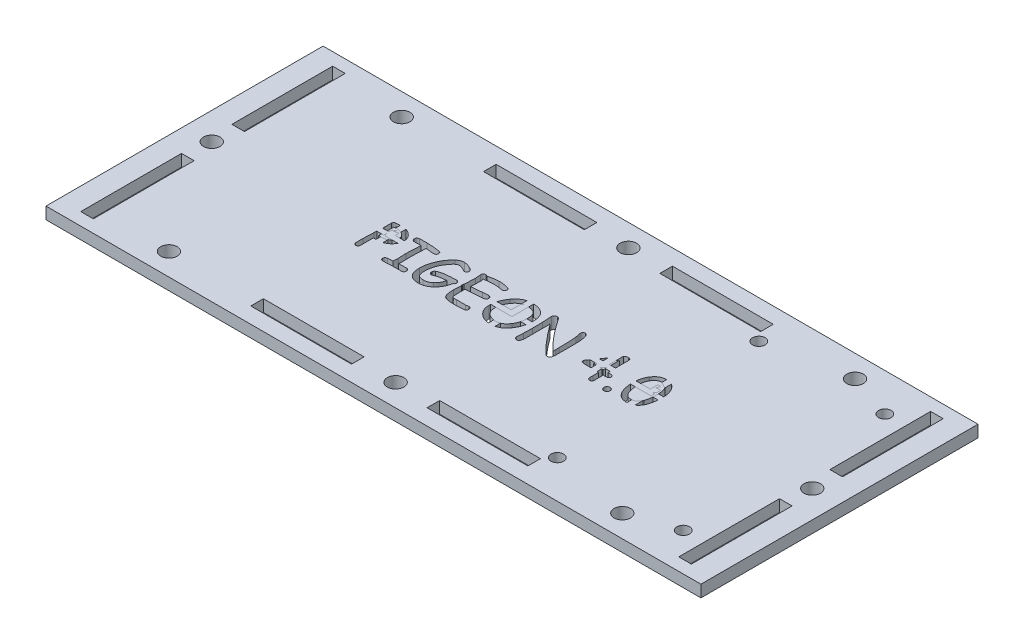
SolidWorks part; units mm, degrees
material "Thornel VCB-20 Carbon Cloth"
ref_plane "Front Plane" through (0, 0, 0) normal (0, 0, 1) x (1, 0, 0)
ref_plane "Top Plane" through (0, 0, 0) normal (0, 1, 0) x (1, 0, 0)
ref_plane "Right Plane" through (0, 0, 0) normal (1, 0, 0) x (0, 0, -1)
sketch "Sketch1" plane through (0, 0, 0) normal (0, 1, 0) x (1, 0, 0)
  line L1 (-82.55, -34.925) -> (82.55, -34.925)
  line L2 (-82.55, -34.925) -> (-82.55, 34.925)
  line L3 (-82.55, 34.925) -> (82.55, 34.925)
  line L4 (82.55, -34.925) -> (82.55, 34.925)
  dimension "D1" = 69.85
  dimension "D2" = 165.1
  dimension "D3" = 34.925
  dimension "D4" = 82.55
extrude "Boss-Extrude1" add sketch "Sketch1" along normal blind 3
sketch "Sketch2" plane through (0, 3, 0) normal (0, 1, 0) x (1, 0, 0)
  line L0 (-82.55, 34.925) -> (-82.55, -34.925) construction
  line L1 (82.55, -34.925) -> (82.55, 34.925) construction
  line L2 (82.55, 34.925) -> (-82.55, 34.925) construction
  line L3 (-82.55, -34.925) -> (82.55, -34.925) construction
  circle A0 centre (-77.47, 29.845) radius 1.5
  circle A1 centre (-77.47, -29.845) radius 1.5
  circle A2 centre (77.47, 29.845) radius 1.5
  circle A3 centre (77.47, -29.845) radius 1.5
  dimension "D1" = 3
  dimension "D2" = 3
  dimension "D3" = 3
  dimension "D4" = 3
  dimension "D5" = 5.08
  dimension "D6" = 5.08
  dimension "D7" = 5.08
  dimension "D8" = 5.08
  dimension "D9" = 5.08
  dimension "D10" = 5.08
  dimension "D11" = 5.08
  dimension "D12" = 5.08
sketch "Sketch3" plane through (0, 3, 0) normal (0, 1, 0) x (1, 0, 0)
  line L0 (-82.55, 34.925) -> (-82.55, -34.925) construction
  line L1 (82.55, -34.925) -> (82.55, 34.925) construction
  line L2 (-82.55, -34.925) -> (82.55, -34.925) construction
  line L3 (82.55, 34.925) -> (-82.55, 34.925) construction
  circle A0 centre (-75.692, 0) radius 2.0828
  circle A1 centre (75.692, 0) radius 2.0828
  circle A2 centre (0, -29.337) radius 2.0828
  circle A3 centre (0, 29.337) radius 2.0828
  circle A4 centre (57.15, 29.337) radius 2.0828
  circle A5 centre (57.15, -29.337) radius 2.0828
  circle A6 centre (-57.15, -29.337) radius 2.0828
  circle A7 centre (-57.15, 29.337) radius 2.0828
  dimension "D1" = 6.858
  dimension "D2" = 6.858
  dimension "D3" = 5.588
  dimension "D4" = 5.588
  dimension "D5" = 2
  dimension "D6" = 2
extrude "Cut-Extrude2" cut sketch "Sketch3" against normal blind 5.08
sketch "Sketch4" plane through (0, 3, 0) normal (0, 1, 0) x (1, 0, 0)
  line L0 (-82.55, 34.925) -> (-82.55, -34.925) construction
  line L1 (-44.31, -29) -> (-67.31, -29) construction
  line L2 (-44.31, -29) -> (-44.31, 29) construction
  line L3 (-44.31, 29) -> (-67.31, 29) construction
  line L4 (-67.31, -29) -> (-67.31, 29) construction
  line L5 (-44.31, -29) -> (-67.31, 29) construction
  line L6 (-44.31, 29) -> (-67.31, -29) construction
  circle A0 centre (-67.31, 29) radius 1.625
  circle A1 centre (-44.31, 29) radius 1.625
  circle A2 centre (-44.31, -29) radius 1.625
  circle A3 centre (-67.31, -29) radius 1.625
  point P0 (-55.81, 0)
  dimension "D3" = 3.25
  dimension "D1" = 58
  dimension "D2" = 23
  dimension "D4" = 15.24
sketch "Sketch5" plane through (0, 3, 0) normal (0, 1, 0) x (1, 0, 0)
  line L0 (82.55, 34.925) -> (-82.55, 34.925) construction
  line L1 (68.58, -25.4) -> (36.83, -25.4) construction
  line L2 (68.58, -25.4) -> (68.58, 25.4) construction
  line L3 (68.58, 25.4) -> (36.83, 25.4) construction
  line L4 (36.83, -25.4) -> (36.83, 25.4) construction
  line L5 (68.58, -25.4) -> (36.83, 25.4) construction
  line L6 (68.58, 25.4) -> (36.83, -25.4) construction
  line L7 (-82.55, -34.925) -> (82.55, -34.925) construction
  line L8 (82.55, -34.925) -> (82.55, 34.925) construction
  circle A0 centre (68.58, -25.4) radius 1.5875
  circle A2 centre (68.58, 25.4) radius 1.5875
  circle A3 centre (36.83, 25.4) radius 1.5875
  circle A4 centre (36.83, -25.4) radius 1.5875
  point P0 (52.705, 0)
  dimension "D1" = 9.525
  dimension "D3" = 3.175
  dimension "D2" = 9.525
  dimension "D4" = 31.75
  dimension "D5" = 13.97
extrude "Cut-Extrude4" cut sketch "Sketch5" against normal blind 7.874
sketch "Sketch6" plane through (0, 3, 0) normal (0, 1, 0) x (1, 0, 0)
  line L0 (82.55, 34.925) -> (-82.55, 34.925) construction
  line L1 (-34.925, 27.7495) -> (-9.525, 27.7495)
  line L2 (-34.925, 27.7495) -> (-34.925, 30.9245)
  line L3 (-34.925, 30.9245) -> (-9.525, 30.9245)
  line L4 (-9.525, 27.7495) -> (-9.525, 30.9245)
  line L5 (-34.925, 27.7495) -> (-9.525, 30.9245) construction
  line L6 (-34.925, 30.9245) -> (-9.525, 27.7495) construction
  line L7 (34.925, 30.9245) -> (34.925, 27.7495)
  line L8 (34.925, 30.9245) -> (9.525, 30.9245)
  line L9 (9.525, 30.9245) -> (9.525, 27.7495)
  line L10 (34.925, 27.7495) -> (9.525, 27.7495)
  line L11 (-34.925, -30.9245) -> (-34.925, -27.7495)
  line L12 (-34.925, -27.7495) -> (-9.525, -27.7495)
  line L13 (-9.525, -30.9245) -> (-9.525, -27.7495)
  line L14 (-34.925, -30.9245) -> (-9.525, -30.9245)
  line L15 (34.925, -27.7495) -> (34.925, -30.9245)
  line L16 (34.925, -27.7495) -> (9.525, -27.7495)
  line L17 (9.525, -27.7495) -> (9.525, -30.9245)
  line L18 (34.925, -30.9245) -> (9.525, -30.9245)
  line L19 (-82.55, 34.925) -> (-82.55, -34.925) construction
  line L20 (-76.962, 31.75) -> (-73.787, 31.75)
  line L21 (-76.962, 31.75) -> (-76.962, 6.35)
  line L22 (-76.962, 6.35) -> (-73.787, 6.35)
  line L23 (-73.787, 31.75) -> (-73.787, 6.35)
  line L24 (-76.962, 31.75) -> (-73.787, 6.35) construction
  line L25 (-76.962, 6.35) -> (-73.787, 31.75) construction
  line L26 (-76.962, -6.35) -> (-76.962, -31.75)
  line L27 (-76.962, -6.35) -> (-73.787, -6.35)
  line L28 (-73.787, -6.35) -> (-73.787, -31.75)
  line L29 (-76.962, -31.75) -> (-73.787, -31.75)
  line L30 (-82.55, -34.925) -> (82.55, -34.925) construction
  line L31 (76.962, -31.75) -> (76.962, -6.35)
  line L32 (76.962, -31.75) -> (73.787, -31.75)
  line L33 (73.787, -31.75) -> (73.787, -6.35)
  line L34 (76.962, -6.35) -> (73.787, -6.35)
  line L35 (76.962, 6.35) -> (76.962, 31.75)
  line L36 (76.962, 31.75) -> (73.787, 31.75)
  line L37 (73.787, 6.35) -> (73.787, 31.75)
  line L38 (76.962, 6.35) -> (73.787, 6.35)
  circle A0 centre (0, 29.337) radius 2.0828 construction
  point P0 (-22.225, 29.337)
  point P9 (-75.3745, 19.05)
  point P16 (0, 29.337)
  point P25 (0, 0)
  point P41 (0, 0)
  point P48 (0, 0)
  dimension "D1" = 5.588
  dimension "D2" = 3.175
  dimension "D3" = 25.4
  dimension "D4" = 22.225
  dimension "D7" = 5.588
  dimension "D8" = 3.175
  dimension "D9" = 25.4
  dimension "D10" = 3.175
  dimension "D12" = 3.175
  dimension "D11" = 2
  dimension "D5" = 2
  dimension "D6" = 2
  dimension "D13" = 2
extrude "Cut-Extrude5" cut sketch "Sketch6" against normal blind 10.922
sketch "Sketch7" plane through (0, 3, 0) normal (0, 1, 0) x (1, 0, 0)
  text T0 "PIGEON 4.0" font "Comic Sans MS" height 9.525
  point P1 (-47.03, 0)
  point P6 (-47.03, 0)
extrude "Cut-Extrude6" cut sketch "Sketch7" against normal blind 10.922
sketch "Sketch8" plane through (0, 3, 0) normal (0, 1, 0) x (1, 0, 0)
  line L0 (-37.8032, 1.2942) -> (-33.6782, 1.2942)
  line L1 (-37.8032, 1.2942) -> (-37.8032, 2.6847)
  line L2 (-37.8032, 2.6847) -> (-33.6782, 2.6847)
  line L3 (-27.9753, 1.2942) -> (-27.9753, 2.6847)
  line L4 (-33.6782, -3.5862) -> (-32.1004, -3.5862)
  line L5 (-33.6782, -3.5862) -> (-33.6782, 1.2942)
  line L6 (-33.6782, 7.5651) -> (-32.1004, 7.5651)
  line L7 (-32.1004, -3.5862) -> (-32.1004, 1.2942)
  line L8 (-32.1004, 2.6847) -> (-27.9753, 2.6847)
  line L9 (-33.6782, 2.6847) -> (-33.6782, 7.5651)
  line L10 (-32.1004, 1.2942) -> (-27.9753, 1.2942)
  line L11 (-32.1004, 2.6847) -> (-32.1004, 7.5651)
  line L12 (-5.3977, -0.3316) -> (-1.2727, -0.3316)
  line L13 (-5.3977, -0.3316) -> (-5.3977, 1.059)
  line L14 (-5.3977, 1.059) -> (-1.2727, 1.059)
  line L15 (4.4302, -0.3316) -> (4.4302, 1.059)
  line L16 (-1.2727, -5.212) -> (0.3051, -5.212)
  line L17 (-1.2727, -5.212) -> (-1.2727, -0.3316)
  line L18 (-1.2727, 5.9393) -> (0.3051, 5.9393)
  line L19 (0.3051, -5.212) -> (0.3051, -0.3316)
  line L20 (0.3051, 1.059) -> (4.4302, 1.059)
  line L21 (-1.2727, 1.059) -> (-1.2727, 5.9393)
  line L22 (0.3051, -0.3316) -> (4.4302, -0.3316)
  line L23 (0.3051, 1.059) -> (0.3051, 5.9393)
  line L24 (17.3249, 0.0958) -> (21.45, 0.0958)
  line L25 (17.3249, 0.0958) -> (17.3249, 1.4864)
  line L26 (17.3249, 1.4864) -> (21.45, 1.4864)
  line L27 (27.1529, 0.0958) -> (27.1529, 1.4864)
  line L28 (21.45, -4.7846) -> (23.0278, -4.7846)
  line L29 (21.45, -4.7846) -> (21.45, 0.0958)
  line L30 (21.45, 6.3667) -> (23.0278, 6.3667)
  line L31 (23.0278, -4.7846) -> (23.0278, 0.0958)
  line L32 (23.0278, 1.4864) -> (27.1529, 1.4864)
  line L33 (21.45, 1.4864) -> (21.45, 6.3667)
  line L34 (23.0278, 0.0958) -> (27.1529, 0.0958)
  line L35 (23.0278, 1.4864) -> (23.0278, 6.3667)
  line L36 (29.4509, -0.1127) -> (33.576, -0.1127)
  line L37 (29.4509, -0.1127) -> (29.4509, 1.2779)
  line L38 (29.4509, 1.2779) -> (33.576, 1.2779)
  line L39 (39.2789, -0.1127) -> (39.2789, 1.2779)
  line L40 (33.576, -4.9931) -> (35.1538, -4.9931)
  line L41 (33.576, -4.9931) -> (33.576, -0.1127)
  line L42 (33.576, 6.1582) -> (35.1538, 6.1582)
  line L43 (35.1538, -4.9931) -> (35.1538, -0.1127)
  line L44 (35.1538, 1.2779) -> (39.2789, 1.2779)
  line L45 (33.576, 1.2779) -> (33.576, 6.1582)
  line L46 (35.1538, -0.1127) -> (39.2789, -0.1127)
  line L47 (35.1538, 1.2779) -> (35.1538, 6.1582)
extrude "Boss-Extrude2" add sketch "Sketch8" against normal up to surface (3 mm away) up to face at (-25.7661, 0, -0.4919)
sketch "Sketch10" plane through (0, 3, 0) normal (0, 1, 0) x (1, 0, 0)
  line L0 (-38.1, 23.495) -> (-19.05, 23.495) construction
  line L1 (-38.1, 24.6856) -> (-19.05, 24.6856)
  line L2 (-38.1, 24.6856) -> (-38.1, 22.3044)
  line L3 (-38.1, 22.3044) -> (-19.05, 22.3044)
  line L4 (-19.05, 24.6856) -> (-19.05, 22.3044)
  line L5 (-28.575, 24.6856) -> (-28.575, 22.3044)
  line L6 (82.55, 34.925) -> (-82.55, 34.925) construction
  line L7 (-82.55, 34.925) -> (-82.55, -34.925) construction
  line L8 (-12.7, 24.6856) -> (-12.7, 22.3044)
  line L9 (-12.7, 24.6856) -> (6.35, 24.6856)
  line L10 (6.35, 24.6856) -> (6.35, 22.3044)
  line L11 (-12.7, 22.3044) -> (6.35, 22.3044)
  line L12 (12.7, 24.6856) -> (12.7, 22.3044)
  line L13 (12.7, 24.6856) -> (31.75, 24.6856)
  line L14 (31.75, 24.6856) -> (31.75, 22.3044)
  line L15 (12.7, 22.3044) -> (31.75, 22.3044)
  line L16 (-12.7, 9.4456) -> (-12.7, 7.0644)
  line L17 (-12.7, 9.4456) -> (6.35, 9.4456)
  line L18 (6.35, 9.4456) -> (6.35, 7.0644)
  line L19 (-12.7, 7.0644) -> (6.35, 7.0644)
  line L20 (12.7, 9.4456) -> (12.7, 7.0644)
  line L21 (12.7, 9.4456) -> (31.75, 9.4456)
  line L22 (31.75, 9.4456) -> (31.75, 7.0644)
  line L23 (12.7, 7.0644) -> (31.75, 7.0644)
  line L24 (-38.1, 9.4456) -> (-38.1, 7.0644)
  line L25 (-38.1, 9.4456) -> (-19.05, 9.4456)
  line L26 (-19.05, 9.4456) -> (-19.05, 7.0644)
  line L27 (-38.1, 7.0644) -> (-19.05, 7.0644)
  line L28 (-38.1, 24.6856) -> (-12.7, 24.6856) construction
  line L29 (0, 0) -> (-82.55, 0) construction
  line L30 (-38.1, -24.6856) -> (-12.7, -24.6856) construction
  line L31 (-38.1, -23.495) -> (-19.05, -23.495) construction
  line L32 (-38.1, -7.0644) -> (-19.05, -7.0644)
  line L33 (-19.05, -9.4456) -> (-19.05, -7.0644)
  line L34 (-38.1, -9.4456) -> (-19.05, -9.4456)
  line L35 (-38.1, -9.4456) -> (-38.1, -7.0644)
  line L36 (12.7, -7.0644) -> (31.75, -7.0644)
  line L37 (31.75, -9.4456) -> (31.75, -7.0644)
  line L38 (12.7, -9.4456) -> (31.75, -9.4456)
  line L39 (12.7, -9.4456) -> (12.7, -7.0644)
  line L40 (-12.7, -7.0644) -> (6.35, -7.0644)
  line L41 (6.35, -9.4456) -> (6.35, -7.0644)
  line L42 (-12.7, -9.4456) -> (6.35, -9.4456)
  line L43 (-12.7, -9.4456) -> (-12.7, -7.0644)
  line L44 (12.7, -22.3044) -> (31.75, -22.3044)
  line L45 (31.75, -24.6856) -> (31.75, -22.3044)
  line L46 (12.7, -24.6856) -> (31.75, -24.6856)
  line L47 (12.7, -24.6856) -> (12.7, -22.3044)
  line L48 (-12.7, -22.3044) -> (6.35, -22.3044)
  line L49 (6.35, -24.6856) -> (6.35, -22.3044)
  line L50 (-12.7, -24.6856) -> (6.35, -24.6856)
  line L51 (-12.7, -24.6856) -> (-12.7, -22.3044)
  line L52 (-28.575, -24.6856) -> (-28.575, -22.3044)
  line L53 (-19.05, -24.6856) -> (-19.05, -22.3044)
  line L54 (-38.1, -22.3044) -> (-19.05, -22.3044)
  line L55 (-38.1, -24.6856) -> (-38.1, -22.3044)
  line L56 (-38.1, -24.6856) -> (-19.05, -24.6856)
  line L57 (8.7313, 11.1125) -> (8.7313, 20.6375)
  line L58 (-16.6687, 11.1125) -> (-15.0812, 11.1125)
  line L59 (-16.6687, 11.1125) -> (-16.6687, 20.6375)
  line L60 (-16.6687, 20.6375) -> (-15.0812, 20.6375)
  line L61 (-15.0812, 11.1125) -> (-15.0812, 20.6375)
  line L62 (-16.6687, 11.1125) -> (-15.0812, 20.6375) construction
  line L63 (-16.6687, 20.6375) -> (-15.0812, 11.1125) construction
  line L64 (8.7313, 11.1125) -> (10.3188, 11.1125)
  line L65 (10.3188, 11.1125) -> (10.3188, 20.6375)
  line L66 (8.7313, 20.6375) -> (10.3188, 20.6375)
  line L67 (-16.6687, 11.1125) -> (8.7313, 11.1125) construction
  line L68 (-16.6687, -20.6375) -> (-15.0812, -20.6375)
  line L69 (-15.0812, -11.1125) -> (-15.0812, -20.6375)
  line L70 (-16.6687, -11.1125) -> (-15.0812, -11.1125)
  line L71 (-16.6687, -11.1125) -> (-16.6687, -20.6375)
  line L72 (8.7313, -11.1125) -> (10.3188, -11.1125)
  line L73 (10.3188, -11.1125) -> (10.3188, -20.6375)
  line L74 (8.7313, -20.6375) -> (10.3188, -20.6375)
  line L75 (8.7313, -11.1125) -> (8.7313, -20.6375)
  line L76 (43.0033, 24.8834) -> (43.0033, 22.5021)
  line L77 (43.0033, 24.8834) -> (62.0533, 24.8834)
  line L78 (62.0533, 24.8834) -> (62.0533, 22.5021)
  line L79 (43.0033, 22.5021) -> (62.0533, 22.5021)
  line L80 (43.0033, 9.6434) -> (43.0033, 7.2621)
  line L81 (43.0033, 9.6434) -> (62.0533, 9.6434)
  line L82 (62.0533, 9.6434) -> (62.0533, 7.2621)
  line L83 (43.0033, 7.2621) -> (62.0533, 7.2621)
  line L84 (17.6033, 24.8834) -> (43.0033, 24.8834) construction
  line L85 (55.7033, 0.1978) -> (-26.8467, 0.1978) construction
  line L86 (17.6033, -24.4879) -> (43.0033, -24.4879) construction
  line L87 (43.0033, -6.8666) -> (62.0533, -6.8666)
  line L88 (62.0533, -9.2479) -> (62.0533, -6.8666)
  line L89 (43.0033, -9.2479) -> (62.0533, -9.2479)
  line L90 (43.0033, -9.2479) -> (43.0033, -6.8666)
  line L91 (43.0033, -22.1066) -> (62.0533, -22.1066)
  line L92 (62.0533, -24.4879) -> (62.0533, -22.1066)
  line L93 (43.0033, -24.4879) -> (62.0533, -24.4879)
  line L94 (43.0033, -24.4879) -> (43.0033, -22.1066)
  line L95 (64.4346, 11.3103) -> (64.4346, 20.8353)
  line L96 (39.0346, 11.3103) -> (40.6221, 11.3103)
  line L97 (39.0346, 11.3103) -> (39.0346, 20.8353)
  line L98 (39.0346, 20.8353) -> (40.6221, 20.8353)
  line L99 (40.6221, 11.3103) -> (40.6221, 20.8353)
  line L100 (39.0346, 11.3103) -> (40.6221, 20.8353) construction
  line L101 (39.0346, 20.8353) -> (40.6221, 11.3103) construction
  line L102 (64.4346, 11.3103) -> (66.0221, 11.3103)
  line L103 (66.0221, 11.3103) -> (66.0221, 20.8353)
  line L104 (64.4346, 20.8353) -> (66.0221, 20.8353)
  line L105 (39.0346, 11.3103) -> (64.4346, 11.3103) construction
  line L106 (39.0346, -20.4397) -> (40.6221, -20.4397)
  line L107 (40.6221, -10.9147) -> (40.6221, -20.4397)
  line L108 (39.0346, -10.9147) -> (40.6221, -10.9147)
  line L109 (39.0346, -10.9147) -> (39.0346, -20.4397)
  line L110 (64.4346, -10.9147) -> (66.0221, -10.9147)
  line L111 (66.0221, -10.9147) -> (66.0221, -20.4397)
  line L112 (64.4346, -20.4397) -> (66.0221, -20.4397)
  line L113 (64.4346, -10.9147) -> (64.4346, -20.4397)
  point P65 (-15.875, 15.875)
  point P105 (39.8283, 16.0728)
  dimension "D1" = 19.05
  dimension "D2" = 2.3813
  dimension "D3" = 11.43
  dimension "D4" = 44.45
  dimension "D7" = 25.4
  dimension "D8" = 15.24
  dimension "D9" = 1.5875
  dimension "D10" = 3.175
  dimension "D11" = 9.525
  dimension "D12" = 7.62
  dimension "D14" = 25.4
  dimension "D15" = 25.4
  dimension "D16" = 1.5875
  dimension "D17" = 9.525
  dimension "D18" = 25.4
  dimension "D5" = 3
  dimension "D6" = 2
  dimension "D13" = 2
